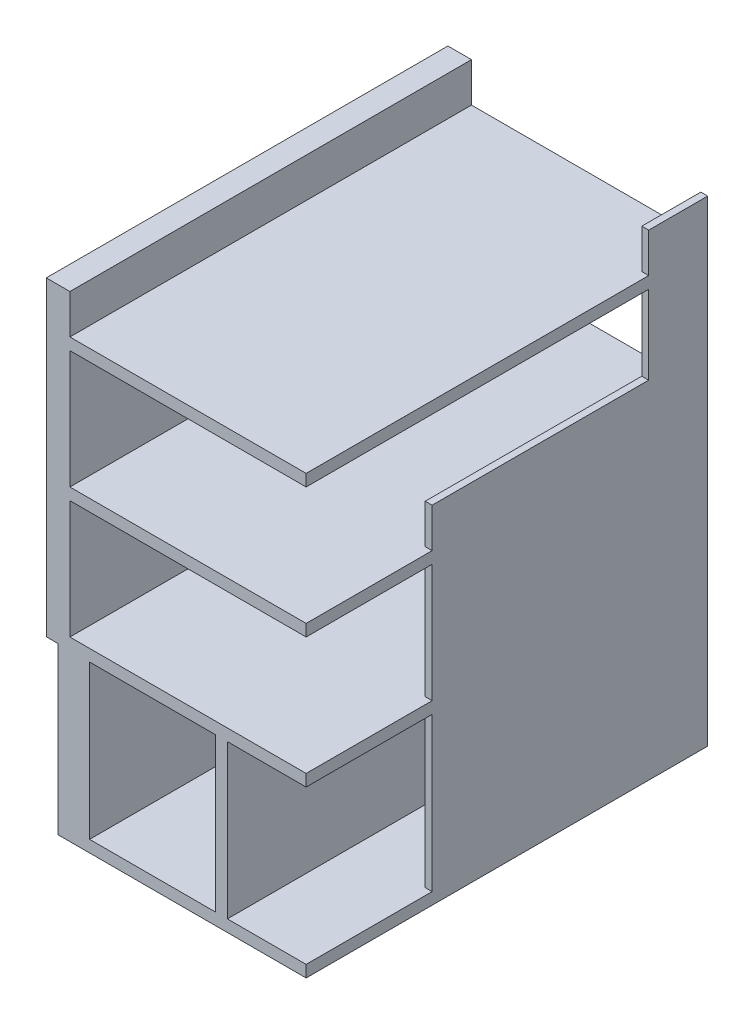
SolidWorks part; units mm, degrees
ref_plane "Front" through (0, 0, 0) normal (0, 0, 1) x (1, 0, 0)
ref_plane "Top" through (0, 0, 0) normal (0, 1, 0) x (1, 0, 0)
ref_plane "Right" through (0, 0, 0) normal (1, 0, 0) x (0, 0, -1)
sketch "Sketch1" plane through (0, 0, 0) normal (0, 0, 1) x (1, 0, 0)
  line L1 (24.3621, 0) -> (24.3621, 121)
  line L2 (24.3621, 121) -> (27.3621, 121)
  line L3 (27.3621, 121) -> (27.3621, 111)
  line L4 (27.3621, 111) -> (87.3621, 111)
  line L5 (87.3621, 111) -> (87.3621, 108)
  line L6 (87.3621, 45) -> (27.3621, 45)
  line L7 (87.3621, 108) -> (27.3621, 108)
  line L8 (27.3621, 108) -> (27.3621, 78)
  line L9 (27.3621, 78) -> (87.3621, 78)
  line L10 (87.3621, 78) -> (87.3621, 75)
  line L11 (87.3621, 3) -> (27.3621, 3)
  line L12 (87.3621, 75) -> (27.3621, 75)
  line L13 (27.3621, 75) -> (27.3621, 45)
  line L14 (27.3621, 42) -> (87.3621, 42)
  line L15 (87.3621, 42) -> (87.3621, 45)
  line L20 (87.3621, 3) -> (87.3621, 0)
  line L24 (24.3621, 0) -> (87.3621, 0)
  line L25 (18.3621, 42) -> (24.3621, 42) construction
  line L26 (18.3621, 42) -> (24.3621, 42) construction
  line L27 (18.3621, 0) -> (24.3621, 0) construction
  line L28 (18.3621, 0) -> (24.3621, 0) construction
  line L29 (27.3621, 45) -> (27.3621, 42) construction
  line L30 (27.3621, 42) -> (27.3621, 3)
  point P1 (0, 0)
  dimension "D1" = 63
  dimension "D2" = 3
  dimension "D3" = 3
  dimension "D4" = 30
  dimension "D5" = 30
  dimension "D6" = 3
  dimension "D7" = 3
  dimension "D8" = 10
extrude "Boss-Extrude1" add sketch "Sketch1" along normal blind 51 and the other way blind 51
sketch "Sketch2" plane through (0, 0, 51) normal (0, 0, 1) x (1, 0, 0)
  line L0 (24.3621, 42.05) -> (21.3621, 42.05)
  line L1 (24.3621, 121) -> (24.3621, 0) construction
  line L2 (21.3621, 42.05) -> (21.3621, 121)
  line L3 (21.3621, 121) -> (24.3621, 121)
  line L4 (24.3621, 42.05) -> (24.3621, 121)
  line L5 (18.3621, 42) -> (24.3621, 42) construction
  dimension "D1" = 3
  dimension "D2" = 0.05
extrude "Boss-Extrude2" add sketch "Sketch2" against normal up to surface (102 mm away) up to face at (53.6955, 64.7778, -51)
sketch "Sketch3" plane through (0, 0, 51) normal (0, 0, 1) x (1, 0, 0)
  line L0 (27.3621, 42) -> (87.3621, 42) construction
  line L1 (27.3621, 3) -> (32.3621, 3)
  line L2 (27.3621, 3) -> (27.3621, 42)
  line L3 (27.3621, 42) -> (32.3621, 42)
  line L4 (32.3621, 3) -> (32.3621, 42)
  line L5 (24.3621, 42.05) -> (24.3621, 0) construction
  line L6 (87.3621, 3) -> (27.3621, 3) construction
  line L7 (67.3621, 3) -> (64.3621, 3)
  line L8 (67.3621, 3) -> (67.3621, 42)
  line L9 (67.3621, 42) -> (64.3621, 42)
  line L10 (64.3621, 3) -> (64.3621, 42)
  dimension "D1" = 8
  dimension "D2" = 3
  dimension "D3" = 32
extrude "Boss-Extrude3" add sketch "Sketch3" against normal up to surface (102 mm away) up to face at (50.4621, 62.505, -51)
sketch "Sketch4" plane through (0, 0, -51) normal (0, 0, -1) x (-1, 0, 0)
  line L1 (-87.3621, 42) -> (-32.3621, 42)
  line L2 (-87.3621, 42) -> (-87.3621, 3)
  line L3 (-87.3621, 3) -> (-32.3621, 3)
  line L4 (-32.3621, 42) -> (-32.3621, 3)
extrude "Boss-Extrude4" add sketch "Sketch4" against normal blind 1
sketch "Sketch5" plane through (87.3621, 0, 0) normal (1, 0, 0) x (0, 0, -1)
  line L0 (36, 0) -> (36, 3)
  line L2 (51, 121) -> (-51, 121) construction
  line L3 (36, 121) -> (51, 121)
  line L4 (51, 121) -> (51, 0)
  line L5 (51, 0) -> (-51, 0) construction
  line L6 (36, 0) -> (51, 0)
  line L7 (-19, 42) -> (-19, 3)
  line L8 (50, 42) -> (-51, 42) construction
  line L9 (50, 3) -> (-51, 3) construction
  line L10 (-19, 3) -> (36, 3)
  line L11 (-19, 42) -> (36, 42) construction
  line L12 (36, 3) -> (36, 42) construction
  line L15 (125.5958, 84.1999) -> (195.5958, 84.1999) construction
  line L16 (125.5958, 84.1999) -> (125.5958, 4.1999) construction
  line L17 (125.5958, 4.1999) -> (195.5958, 4.1999) construction
  line L18 (195.5958, 84.1999) -> (195.5958, 4.1999) construction
  line L19 (36, 75) -> (-19, 75) construction
  line L20 (-19, 75) -> (-19, 88)
  line L21 (-19, 88) -> (36, 88)
  line L22 (51, 75) -> (-51, 75) construction
  line L24 (-19, 42) -> (-19, 75)
  line L28 (36, 88) -> (36, 121)
  point P28 (36, 88)
  point P29 (0, 0)
  point P30 (0, 0)
  point P31 (0, 0)
  point P32 (0, 0)
  dimension "D1" = 15
  dimension "D2" = 70
  dimension "D3" = 80
  dimension "D4" = 70
  dimension "D5" = 13
extrude "Boss-Extrude5" add sketch "Sketch5" against normal blind 1.75
sketch "Sketch7" plane through (24.3621, 0, 0) normal (-1, 0, 0) x (0, 0, 1)
  circle A0 centre (-29.3621, 37) radius 1.8
  circle A1 centre (-29.3621, 10) radius 1.8
  circle A2 centre (29.3621, 10) radius 1.8
  circle A3 centre (29.3621, 37) radius 1.8
  point P8 (0, 0)
  dimension "D1" = 3.6
extrude "Cut-Extrude1" cut sketch "Sketch7" against normal blind 6
